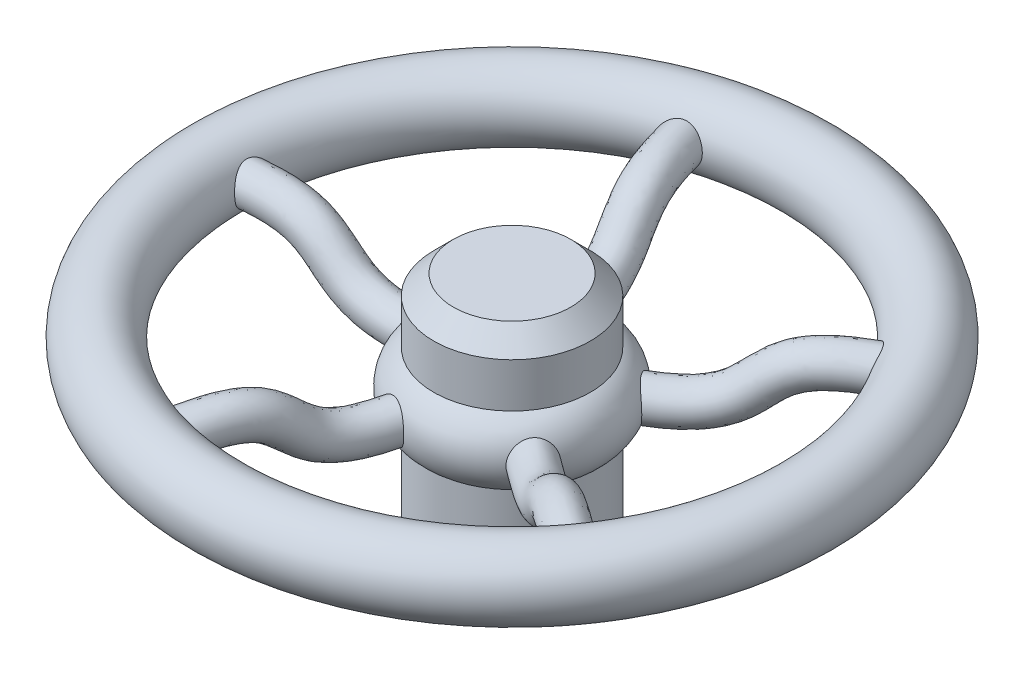
SolidWorks part; units mm, degrees
ref_plane "Front Plane" through (0, 0, 0) normal (0, 0, 1) x (1, 0, 0)
ref_plane "Top Plane" through (0, 0, 0) normal (0, 1, 0) x (1, 0, 0)
ref_plane "Right Plane" through (0, 0, 0) normal (1, 0, 0) x (0, 0, -1)
sketch "Sketch1" plane through (0, 0, 0) normal (0, 0, 1) x (1, 0, 0)
  line L0 (-22.1854, 28.1492) -> (-28.5354, 21.7992)
  line L1 (-3.1354, 28.1492) -> (-22.1854, 28.1492)
  line L2 (-3.1354, 28.1492) -> (-3.1354, -48.0508)
  line L3 (-3.1354, -48.0508) -> (-28.5354, -48.0508)
  line L4 (-28.5354, 21.7992) -> (-28.5354, -48.0508)
  circle A0 centre (-22.1854, -3.6008) radius 12.7
  point P3 (-28.5354, 28.1492)
  point P8 (0, 0)
  dimension "D5" = 25.4
  dimension "D1" = 25.4
  dimension "D2" = 76.2
  dimension "D4" = 44.45
revolve "Revolve1" add sketch "Sketch1" angle 360 about L2 region at (-12.6604, 27.346, 0) region at (-20.0096, -3.6008, 0) region at (-31.1392, -3.6008, 0)
sketch "Sketch2" plane through (0, 0, 0) normal (0, 0, 1) x (1, 0, 0)
  line L0 (-3.1354, -48.0508) -> (-3.1354, -1.4494) construction
  line L1 (-28.5354, -48.0508) -> (22.2646, -48.0508) construction
  arc A0 (-28.5354, 7.3977) -> (-28.5354, -14.5993) centre (-22.1854, -3.6008) ccw construction
  spline S0 degree 3 poles (-3.1354, -1.4494) (-17.153, 1.0781) (-46.6506, -11.496) (-70.2362, 14.7288) (-88.4911, 10.3117) (-98.4645, 10.2342) knots 0 0 0 0 0.530708 0.677139 1 1 1 1
  point P5 (-55.0815, 0)
  point P7 (-88.3718, 10.8557)
ref_plane "Plane1" through (-98.4645, 10.2342, 0) normal (-1, -0.0078, 0) x (0, 0, 1)
sketch "Sketch3" plane through (-98.4645, 10.2342, 0) normal (-1, -0.0078, 0) x (0, 0, 1)
sweep "Sweep1" add path "Sketch2" circular profile diameter 12.7 parameters "D3"=12.7
pattern_circular "CirPattern1" count 5 over 360 about axis through (-3.1354, 28.1492, 0) along (0, 1, 0) of "Sweep1" reverse direction yes
sketch "Sketch17" plane through (0, 0, 0) normal (0, 0, 1) x (1, 0, 0)
  line L0 (-98.5139, 16.584) -> (-98.4152, 3.8844) construction
  line L1 (-3.1354, -48.0508) -> (-3.1354, 41.5428) construction
  line L2 (-28.5354, -48.0508) -> (22.2646, -48.0508) construction
  circle A0 centre (-98.4645, 10.2342) radius 11.5289
revolve "Revolve2" add sketch "Sketch17" angle 360 about L1
hole_wizard "CBORE for 3/8 Hex Head Bolt2" positions "Sketch22" profile "Sketch23" counterbore size "3/8" standard "ANSI Inch"
sketch "Sketch22" plane through (0, -48.0508, 0) normal (0, -1, 0) x (-1, 0, 0)
  point P0 (3.1354, 0)
sketch "Sketch23" plane through (-3.1354, -48.0508, 0) normal (1, 0, 0) x (0, 0, -1)
  line L0 (0, 0) -> (0, 41.1295)
  line L1 (0, 41.1295) -> (5.0419, 38.1)
  line L2 (5.0419, 38.1) -> (5.0419, 6.8072)
  line L3 (5.0419, 6.8072) -> (11.1125, 6.8072)
  line L5 (11.1125, 6.8072) -> (11.1125, 0.5328)
  line L6 (11.1125, 0.5328) -> (11.7475, 0)
  line L7 (11.7475, 0) -> (0, 0)
  line L8 (-11.1125, 0.5328) -> (-11.7475, 0) construction
  line L10 (0, 41.1295) -> (-5.0419, 38.1) construction
  line L11 (0, -6.35) -> (0, 107.95) construction
  dimension "Hole Dia." = 10.0838
  dimension "Hole Depth" = 38.1
  dimension "C'Bore Dia." = 22.225
  dimension "C'Bore Depth" = 6.8072
  dimension "Near C'Sink Dia." = 23.495
  dimension "Near C'Sink Angle" = 100
  dimension "Drill Angle" = 118
